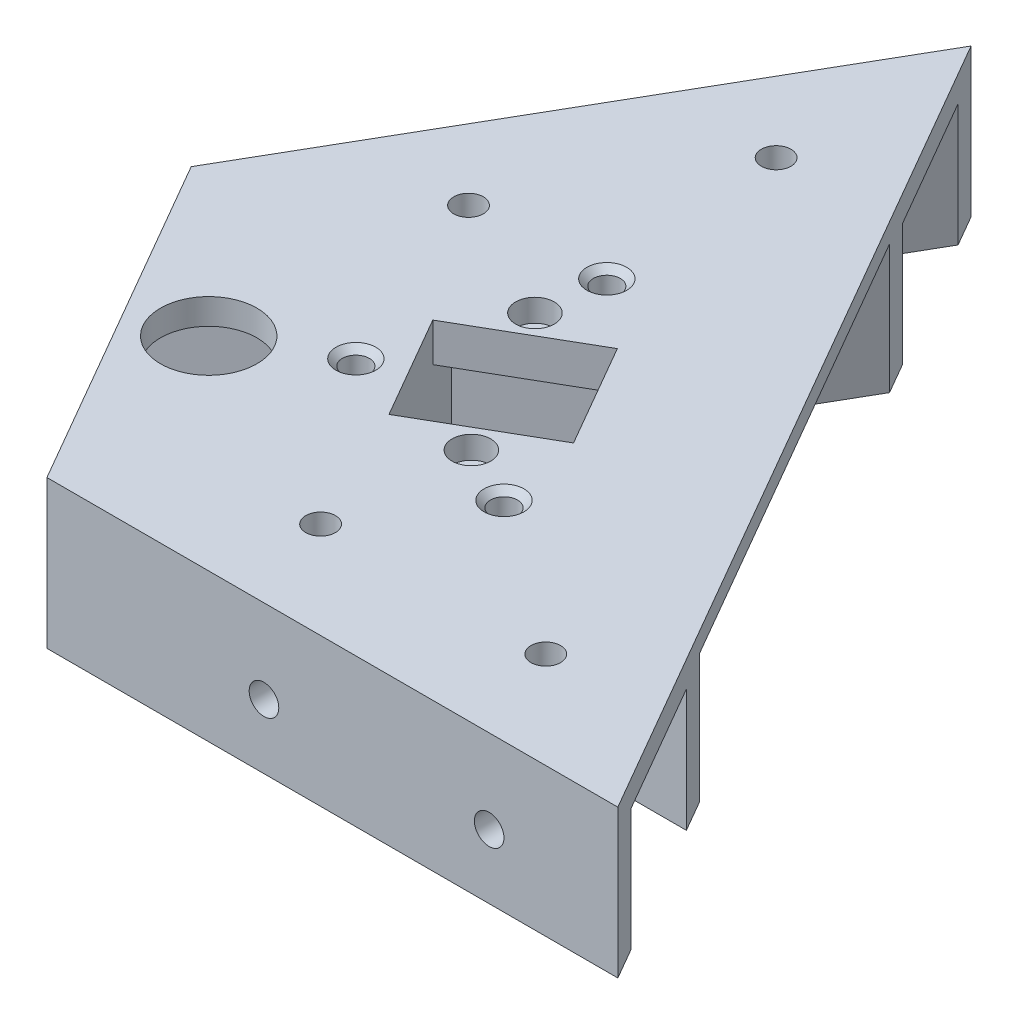
SolidWorks part; units mm, degrees
other "Markup1"
sketch "Sketch26" plane through (25.6218, 0, -129.9038) normal (-0.1134, -0.9932, -0.0259) x (0.9576, -0.1162, 0.2636)
ref_plane "Front Plane" through (0, 0, 0) normal (0, 0, 1) x (1, 0, 0)
ref_plane "Top Plane" through (0, 0, 0) normal (0, 1, 0) x (1, 0, 0)
ref_plane "Right Plane" through (0, 0, 0) normal (1, 0, 0) x (0, 0, -1)
sketch "Sketch1" plane through (0, 0, 0) normal (0, 1, 0) x (1, 0, 0)
  line L0 (0, 0) -> (150, 0)
  line L1 (0, 0) -> (75, 129.9038)
  line L2 (75, 129.9038) -> (150, 0)
  dimension "D1" = 60
  dimension "D2" = 150
  dimension "D3" = 60
extrude "Boss-Extrude1" add sketch "Sketch1" along normal blind 23
sketch "Sketch2" plane through (0, 0, 0) normal (0, 1, 0) x (1, 0, 0)
  line L0 (0, 0) -> (150, 0) construction
  line L1 (74, 5) -> (174, 5) construction
  line L2 (74, 5) -> (74, 25) construction
  line L3 (74, 25) -> (174, 25) construction
  line L4 (174, 5) -> (174, 25) construction
  line L5 (41.3301, 61.5859) -> (91.3301, 148.1884) construction
  line L6 (91.3301, 148.1884) -> (108.6506, 138.1884) construction
  line L7 (108.6506, 138.1884) -> (58.6506, 51.5859) construction
  line L8 (58.6506, 51.5859) -> (41.3301, 61.5859) construction
  line L9 (75, 129.9038) -> (0, 0) construction
  line L10 (108.9238, 138.2616) -> (58.7238, 51.3127)
  line L11 (58.7238, 51.3127) -> (41.0569, 61.5127)
  line L12 (41.0569, 61.5127) -> (91.2569, 148.4616)
  line L13 (91.2569, 148.4616) -> (108.9238, 138.2616)
  line L14 (73.8, 25.2) -> (174.2, 25.2)
  line L15 (174.2, 4.8) -> (174.2, 25.2)
  line L16 (73.8, 4.8) -> (174.2, 4.8)
  line L17 (73.8, 4.8) -> (73.8, 25.2)
  dimension "D1" = 20
  dimension "D2" = 5
  dimension "D3" = 74
  dimension "D4" = 20
  dimension "D5" = 74
  dimension "D6" = 5
  dimension "D7" = 100
  dimension "D8" = 100
  dimension "D9" = 0.2
  dimension "D10" = 0.2
extrude "Cut-Extrude2" cut sketch "Sketch2" along normal blind 19
sketch "Sketch4" plane through (0, 0, 0) normal (0, 1, 0) x (1, 0, 0)
  line L4 (135.4508, 25.2) -> (89.5492, 104.7038) construction
  line L5 (41.1219, 35.2887) -> (0, 0) construction
  line L6 (0, 0) -> (52.9457, 91.7047) construction
  line L7 (68.4424, 27.9682) -> (51.1219, 17.9682) construction
  line L8 (68.4424, 27.9682) -> (58.4424, 45.2887) construction
  line L9 (58.4424, 45.2887) -> (41.1219, 35.2887) construction
  line L10 (51.1219, 17.9682) -> (41.1219, 35.2887) construction
  line L11 (68.4424, 27.9682) -> (41.1219, 35.2887) construction
  line L12 (58.4424, 45.2887) -> (51.1219, 17.9682) construction
  line L13 (58.5156, 45.5619) -> (40.8487, 35.3619)
  line L14 (75, 129.9038) -> (0, 0) construction
  line L15 (0, 0) -> (130.8784, 0) construction
  line L16 (0, 0) -> (150, 0) construction
  line L17 (51.0487, 17.695) -> (40.8487, 35.3619)
  line L18 (68.7156, 27.895) -> (51.0487, 17.695)
  line L19 (68.7156, 27.895) -> (58.5156, 45.5619)
  line L20 (51.1219, 17.9682) -> (0, 0) construction
  point P0 (54.7821, 31.6285)
  dimension "D1" = 20
  dimension "D2" = 20
  dimension "D3" = 21.269
  dimension "D4" = 0.2
  dimension "D5" = 54.1877
  dimension "D6" = 19.365
extrude "Cut-Extrude3" cut sketch "Sketch4" along normal blind 19
sketch "Sketch7" plane through (0, 0, 0) normal (-0.866, 0, -0.5) x (-0.5, 0, 0.866)
  line L0 (-150, 0) -> (0, 0) construction
  line L1 (-150, 23) -> (-150, 0) construction
  circle A0 centre (-130, 10) radius 2.3
  circle A1 centre (-95, 10) radius 2.3
  dimension "D1" = 4.6
  dimension "D2" = 10
  dimension "D3" = 20
  dimension "D4" = 35
extrude "Cut-Extrude6" cut sketch "Sketch7" against normal blind 10
sketch "Sketch8" plane through (0, 0, 0) normal (0, 0, 1) x (1, 0, 0)
  line L0 (150, 23) -> (150, 0) construction
  line L1 (0, 0) -> (150, 0) construction
  circle A0 centre (130, 10) radius 2.3
  circle A1 centre (95, 10) radius 2.3
  dimension "D1" = 4.6
  dimension "D2" = 20
  dimension "D3" = 10
  dimension "D4" = 35
extrude "Cut-Extrude7" cut sketch "Sketch8" against normal blind 10
ref_plane "Plane1" through (42.4846, 0, -24.5285) normal (0.866, 0, -0.5) x (-0.5, 0, -0.866)
sketch "Sketch22" plane through (0, 0, 0) normal (0, -1, 0) x (1, 0, 0)
  line L0 (83.3534, -28.1478) -> (66.0534, -58.1122)
  line L1 (66.0534, -58.1122) -> (84.2399, -68.6122)
  line L2 (84.2399, -68.6122) -> (101.5399, -38.6478)
  line L3 (101.5399, -38.6478) -> (83.3534, -28.1478)
  line L5 (135.4508, -25.2) -> (89.5492, -104.7038) construction
  dimension "D1" = 86.26
  dimension "D2" = 17.3
  dimension "D3" = 17.3
  dimension "D4" = 21
extrude "Cut-Extrude11" cut sketch "Sketch22" against normal through all both and the other way through all
sketch "Sketch21" plane through (0, 0, 0) normal (0, -1, 0) x (1, 0, 0)
  line L0 (132.6795, -30) -> (109.9968, -30)
  line L1 (109.9968, -30) -> (80.9791, -80.26)
  line L2 (80.9791, -80.26) -> (92.3205, -99.9038)
  line L3 (92.3205, -99.9038) -> (132.6795, -30)
  line L4 (135.4508, -25.2) -> (89.5492, -104.7038) construction
  line L5 (135.4508, -25.2) -> (73.8, -25.2) construction
  line L7 (58.7238, -51.3127) -> (89.5492, -104.7038) construction
  line L8 (58.7238, -51.3127) -> (89.5492, -104.7038) construction
  line L9 (84.2399, -68.6122) -> (101.5399, -38.6478) construction
  dimension "D1" = 3
  dimension "D2" = 4.8
  dimension "D3" = 4.8
extrude "Cut-Extrude10" cut sketch "Sketch21" against normal offset from surface (20 mm away) 3 up to face at (83.7966, 23, -48.38)
sketch "Sketch32" plane through (0, 0, -30) normal (0, 0, -1) x (-1, 0, 0)
  line L0 (-132.6795, 10) -> (-109.9968, 10) construction
  line L1 (-132.6795, 20) -> (-132.6795, 0) construction
  line L2 (-109.9968, 20) -> (-109.9968, 0) construction
  circle A0 centre (-121.3381, 10) radius 2.3
  dimension "D1" = 4.6
extrude "Cut-Extrude18" cut sketch "Sketch32" against normal blind 10
sketch "Sketch33" plane through (25.9808, 0, 15) normal (0.866, 0, 0.5) x (0.5, 0, -0.866)
  line L0 (109.9968, 10) -> (132.6795, 10) construction
  line L1 (109.9968, 20) -> (109.9968, 0) construction
  line L2 (132.6795, 20) -> (132.6795, 0) construction
  circle A0 centre (121.3381, 10) radius 2.3
  dimension "D1" = 4.6
extrude "Cut-Extrude19" cut sketch "Sketch33" against normal blind 10
sketch "Sketch34" plane through (45.9487, 0, -26.5285) normal (0.866, 0, -0.5) x (-0.5, 0, -0.866)
  line L0 (-10.2, 9.5) -> (10.2, 9.5) construction
  line L1 (-10.2, 19) -> (-10.2, 0) construction
  line L2 (10.2, 19) -> (10.2, 0) construction
  circle A0 centre (0, 9.5) radius 2.3
  dimension "D1" = 4.6
extrude "Cut-Extrude20" cut sketch "Sketch34" against normal through all
ref_plane "Plane2" through (43.3506, 0, -25.0285) normal (0.866, 0, -0.5) x (-0.5, 0, -0.866)
sketch "Sketch35" plane through (43.3506, 0, -25.0285) normal (0.866, 0, -0.5) x (-0.5, 0, -0.866)
  circle A0 centre (0, 9.5) radius 4
  dimension "D1" = 8
extrude "Cut-Extrude21" cut sketch "Sketch35" against normal through all
sketch "Sketch36" plane through (0, 23, 0) normal (0, 1, 0) x (1, 0, 0)
  line L0 (0, 0) -> (112.5, 64.9519) construction
  line L1 (150, 0) -> (75, 129.9038) construction
  circle A0 centre (69.282, 40) radius 2.1
  dimension "D1" = 4.2
  dimension "D2" = 80
extrude "Cut-Extrude22" cut sketch "Sketch36" against normal through all
sketch "Sketch38" plane through (0, 19, 0) normal (0, -1, 0) x (1, 0, 0)
  line L0 (49.8904, -56.4127) -> (83.6603, -114.9038) construction
  line L1 (41.0569, -61.5127) -> (58.7238, -51.3127) construction
  line L2 (77.7713, -125.1038) -> (89.5492, -104.7038) construction
  line L3 (73.8, -15) -> (141.3397, -15) construction
  line L4 (73.8, -25.2) -> (73.8, -4.8) construction
  line L5 (135.4508, -25.2) -> (147.2287, -4.8) construction
  line L6 (41.0569, -61.5127) -> (58.7238, -51.3127) construction
  circle A0 centre (88.8, -15) radius 2.3
  circle A1 centre (123.8, -15) radius 2.3
  circle A2 centre (57.3904, -69.4031) radius 2.3
  circle A3 centre (74.8904, -99.7139) radius 2.3
  dimension "D1" = 4.6
  dimension "D2" = 15
  dimension "D3" = 35
  dimension "D4" = 15
  dimension "D5" = 35
extrude "Cut-Extrude24" cut sketch "Sketch38" against normal blind 10
sketch "Sketch39" plane through (0, 23, 0) normal (0, 1, 0) x (1, 0, 0)
  line L0 (66.0534, 58.1122) -> (84.2399, 68.6122)
  line L1 (84.2399, 68.6122) -> (88.2399, 61.684)
  line L2 (84.2399, 68.6122) -> (101.5399, 38.6478) construction
  line L3 (88.2399, 61.684) -> (70.0534, 51.184)
  line L4 (83.3534, 28.1478) -> (66.0534, 58.1122) construction
  line L5 (70.0534, 51.184) -> (66.0534, 58.1122)
  line L6 (101.5399, 38.6478) -> (83.3534, 28.1478)
  line L7 (83.3534, 28.1478) -> (79.3534, 35.076)
  line L8 (79.3534, 35.076) -> (97.5399, 45.576)
  line L9 (97.5399, 45.576) -> (101.5399, 38.6478)
  dimension "D1" = 8
  dimension "D2" = 8
extrude "Boss-Extrude2" add sketch "Sketch39" against normal blind 6
sketch "Sketch40" plane through (0, 17, 0) normal (0, -1, 0) x (1, 0, 0)
  line L0 (92.4466, -33.3978) -> (75.1466, -63.3622) construction
  line L1 (101.5399, -38.6478) -> (83.3534, -28.1478) construction
  line L2 (66.0534, -58.1122) -> (84.2399, -68.6122) construction
  line L3 (84.2399, -68.6122) -> (66.0534, -58.1122) construction
  circle A0 centre (90.5466, -36.6887) radius 1.65
  circle A1 centre (77.0466, -60.0713) radius 1.65
  dimension "D1" = 3.3
  dimension "D2" = 3.3
  dimension "D3" = 3.8
  dimension "D4" = 3.8
extrude "Cut-Extrude25" cut sketch "Sketch40" against normal through all
sketch "Sketch41" plane through (0, 23, 0) normal (0, 1, 0) x (1, 0, 0)
  circle A0 centre (77.0466, 60.0713) radius 3
  circle A1 centre (90.5466, 36.6887) radius 3
  dimension "D1" = 6
extrude "Cut-Extrude26" cut sketch "Sketch41" against normal blind 3.5
sketch "Sketch42" plane through (0, 23, 0) normal (0, 1, 0) x (1, 0, 0)
  line L0 (0, 0) -> (98.694, 88.8645) construction
  line L1 (150, 0) -> (75, 129.9038) construction
  line L2 (0, 0) -> (126.306, 41.0393) construction
  line L3 (0, 0) -> (112.5, 64.9519) construction
  line L4 (132.6795, 30) -> (92.3205, 99.9038) construction
  circle A0 centre (99.8609, 32.4468) radius 2.1
  circle A1 centre (78.0302, 70.2587) radius 2.1
  dimension "D5" = 4.2
  dimension "D1" = 12
  dimension "D2" = 12
  dimension "D3" = 105
  dimension "D4" = 105
extrude "Cut-Extrude27" cut sketch "Sketch42" against normal through all
chamfer "Chamfer2" distance 1 angle 45 3 edges at (78.0302, 23, -68.1587) (69.282, 23, -37.9) (99.8609, 23, -30.3468)
sketch "Sketch43" plane through (0, 0, 0) normal (0, -1, 0) x (1, 0, 0)
  line L0 (59.8821, -22.795) -> (49.6821, -40.4619) construction
  line L3 (51.0487, -17.695) -> (68.7156, -27.895) construction
  line L4 (58.5156, -45.5619) -> (40.8487, -35.3619) construction
  line L5 (49.6821, -40.4619) -> (59.8821, -22.795) construction
  line L6 (58.5156, -45.5619) -> (40.8487, -35.3619) construction
  circle A0 centre (64.3821, -15.0008) radius 2.1
  circle A1 centre (45.1821, -48.2562) radius 2.1
  point P7 (54.7821, -31.6285)
  dimension "D1" = 4.2
  dimension "D2" = 9
  dimension "D3" = 9
extrude "Cut-Extrude28" cut sketch "Sketch43" against normal blind 15
chamfer "Chamfer3" distance 1 angle 45 2 edges at (64.3821, 0, -17.1008) (45.1821, 0, -50.3562)
ref_plane "Plane3" through (66.2137, 0, -38.2285) normal (-0.866, 0, 0.5) x (0.5, 0, 0.866)
sketch "Sketch45" plane through (63.6156, 0, -36.7285) normal (-0.866, 0, 0.5) x (0.5, 0, 0.866)
  line L0 (-10.2, 9.5) -> (10.2, 9.5) construction
  line L1 (-10.2, 19) -> (-10.2, 0) construction
  line L2 (10.2, 19) -> (10.2, 0) construction
  circle A0 centre (0, 9.5) radius 2.3
  dimension "D1" = 4.6
extrude "Cut-Extrude29" cut sketch "Sketch45" against normal through all
sketch "Sketch46" plane through (66.2137, 0, -38.2285) normal (-0.866, 0, 0.5) x (0.5, 0, 0.866)
  circle A0 centre (0, 9.5) radius 4
extrude "Cut-Extrude30" cut sketch "Sketch46" against normal through all
sketch "Sketch47" plane through (0, 19, 0) normal (0, -1, 0) x (1, 0, 0)
  line L0 (59.8821, -22.795) -> (49.6821, -40.4619) construction
  line L1 (51.0487, -17.695) -> (68.7156, -27.895) construction
  line L2 (58.5156, -45.5619) -> (40.8487, -35.3619) construction
  line L3 (45.9487, -26.5285) -> (63.6156, -36.7285) construction
  line L4 (40.8487, -35.3619) -> (51.0487, -17.695) construction
  line L5 (68.7156, -27.895) -> (58.5156, -45.5619) construction
  circle A0 centre (54.7821, -31.6285) radius 7.5
  dimension "D1" = 15
extrude "Cut-Extrude31" cut sketch "Sketch47" against normal blind 10
sketch "Sketch48" plane through (0, 0, 0) normal (0, -1, 0) x (1, 0, 0)
  line L0 (61.2649, 0) -> (30.6324, -53.0569)
  line L1 (0, 0) -> (150, 0) construction
  line L2 (75, -129.9038) -> (0, 0) construction
  line L3 (40.8487, -35.3619) -> (51.0487, -17.695) construction
  line L4 (61.2649, 0) -> (0, 0)
  line L5 (0, 0) -> (30.6324, -53.0569)
extrude "Cut-Extrude32" cut sketch "Sketch48" against normal through all
